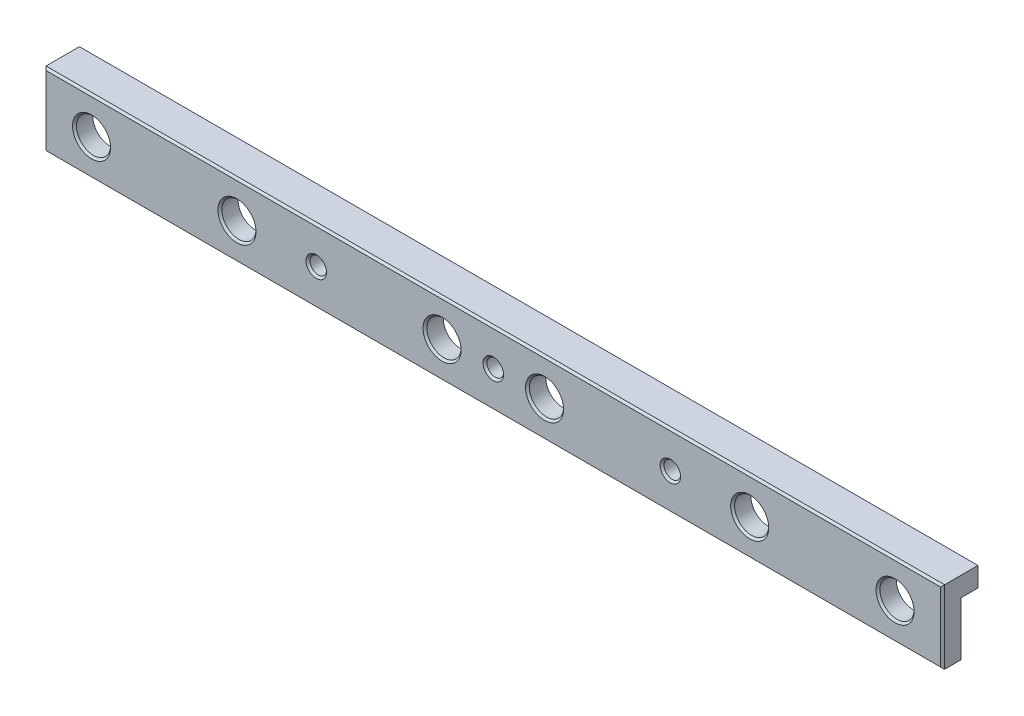
SolidWorks part; units mm, degrees
ref_plane "Front Plane" through (0, 0, 0) normal (0, 0, 1) x (1, 0, 0)
ref_plane "Top Plane" through (0, 0, 0) normal (0, 1, 0) x (1, 0, 0)
ref_plane "Right Plane" through (0, 0, 0) normal (1, 0, 0) x (0, 0, -1)
sketch "Sketch1" plane through (0, 0, 0) normal (0, 0, 1) x (1, 0, 0)
  line L0 (0, 7.5) -> (0, 0) construction
  line L1 (92, 7.5) -> (-92, 7.5)
  line L2 (92, 7.5) -> (92, 3.5)
  line L3 (92, -7.5) -> (-92, -7.5)
  line L4 (-92, 7.5) -> (-92, 3.5)
  line L5 (92, 3.5) -> (-92, 3.5)
  line L6 (-92, 3.5) -> (-92, -7.5)
  line L7 (92, 3.5) -> (92, -7.5)
  line L8 (0, 0) -> (0, -7.5) construction
  dimension "D1" = 92
  dimension "D2" = 7.5
  dimension "D3" = 4
extrude "Boss-Extrude1" add sketch "Sketch1" against normal blind 7.25 contours L7 L5 L6 L3 | L1 L0 L5 L2 | L0 L1 L4 L5 region at (0, 5.5, 0) region at (0, -2, 0)
extrude "Cut-Extrude1" cut sketch "Sketch1<6>" along normal blind 3.5 from surface contours L7 L5 L6 L3 region at (0, -2, 0) starting at face at (0, 0, -7.25)
sketch "Sketch1<6>" plane through (0, 0, 0) normal (0, 0, 1) x (1, 0, 0) same geometry as "Sketch1"
sketch "Sketch2" plane through (0, 0, 0) normal (0, 0, 1) x (1, 0, 0)
  line L0 (0, 7.5) -> (0, 0) construction
  circle A0 centre (-52.5, 0) radius 3.5
  circle A8 centre (-36.25, 0) radius 1.7
  circle A9 centre (-10.5, 0) radius 3.5
  circle A12 centre (0, 0) radius 1.7
  circle A13 centre (10.5, 0) radius 3.5
  circle A14 centre (36.25, 0) radius 1.7
  circle A15 centre (52.5, 0) radius 3.5
  circle A16 centre (-82.27, 0) radius 3.5
  circle A17 centre (82.27, 0) radius 3.5
  point P17 (-1.6887, 6.7853)
  dimension "D2" = 7
  dimension "D4" = 29.77
  dimension "D3" = 7
  dimension "D1" = 3.4
extrude "Cut-Extrude2" cut sketch "Sketch2" against normal through all both and the other way through all
chamfer "Chamfer1" distance 0.4 angle 45 13 edges at (0, -7.5, 0) (-92, 0, 0) (0, 7.5, 0) (92, 0, 0) (56, 0, 0) (37.95, 0, 0) (14, 0, 0) (1.7, 0, 0) (-7, 0, 0) (-34.55, 0, 0) (-49, 0, 0) (-78.77, 0, 0) (85.77, 0, 0)
